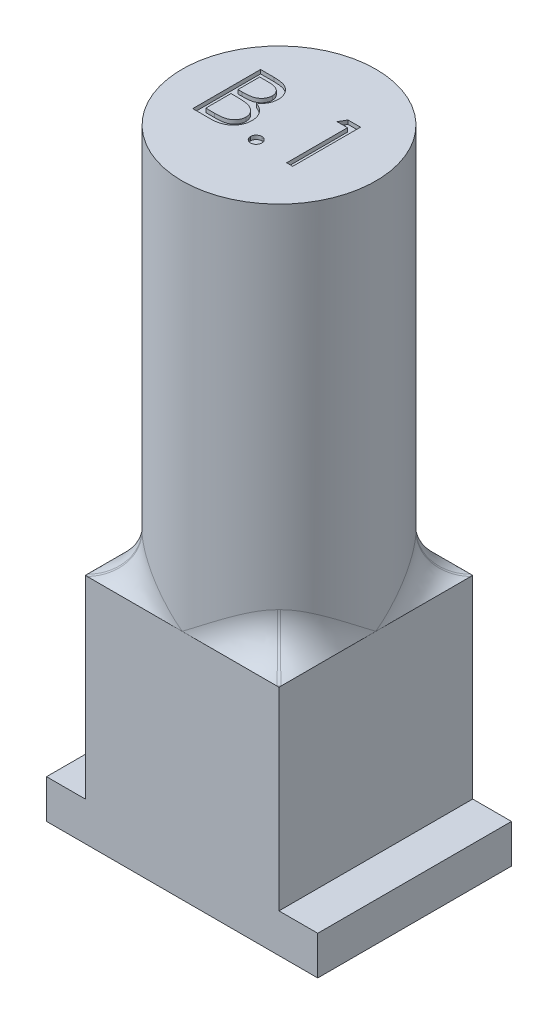
SolidWorks part; units mm, degrees
material "ABS"
ref_plane "Front Plane" through (0, 0, 0) normal (0, 0, 1) x (1, 0, 0)
ref_plane "Top Plane" through (0, 0, 0) normal (0, 1, 0) x (1, 0, 0)
ref_plane "Right Plane" through (0, 0, 0) normal (1, 0, 0) x (0, 0, -1)
sketch "Sketch1" plane through (0, 0, 0) normal (0, 1, 0) x (1, 0, 0)
  line L0 (-5, 5) -> (5, 5)
  line L1 (5, 5) -> (5, -5)
  line L2 (5, -5) -> (-5, -5)
  line L3 (-5, -5) -> (-5, 5)
  line L4 (-5, 0) -> (5, 0) construction
  line L5 (0, 5) -> (0, -5) construction
  circle A0 centre (0, 0) radius 5 construction
  dimension "D1" = 10
extrude "Boss-Extrude1" add sketch "Sketch1" along normal blind 12
sketch "Sketch2" plane through (0, 12, 0) normal (0, 1, 0) x (1, 0, 0)
  circle A0 centre (0, 0) radius 5
extrude "Boss-Extrude2" add sketch "Sketch2" along normal blind 20.13
sketch "Sketch3" plane through (-5, 0, 0) normal (-1, 0, 0) x (0, 0, 1)
  line L0 (-5, 0) -> (5, 0) construction
  line L1 (-5, 0) -> (5, 0)
  line L2 (-5, 2) -> (5, 2)
  line L3 (-5, 2) -> (-5, 0)
  line L4 (5, 2) -> (5, 0)
  dimension "D1" = 2
extrude "Boss-Extrude3" add sketch "Sketch3" along normal blind 2
mirror "Mirror1" about plane through (0, 0, 0) normal (1, 0, 0) of "Boss-Extrude3"
fillet "Fillet1" radius 2 4 edges at (3.5355, 12, 3.5355) (3.5355, 12, -3.5355) (-3.5355, 12, -3.5355) (-3.5355, 12, 3.5355)
sketch "Sketch4" plane through (0, 32.13, 0) normal (0, 1, 0) x (1, 0, 0)
  text T0 "B.1"
extrude "Cut-Extrude1" cut sketch "Sketch4" against normal blind 0.2
